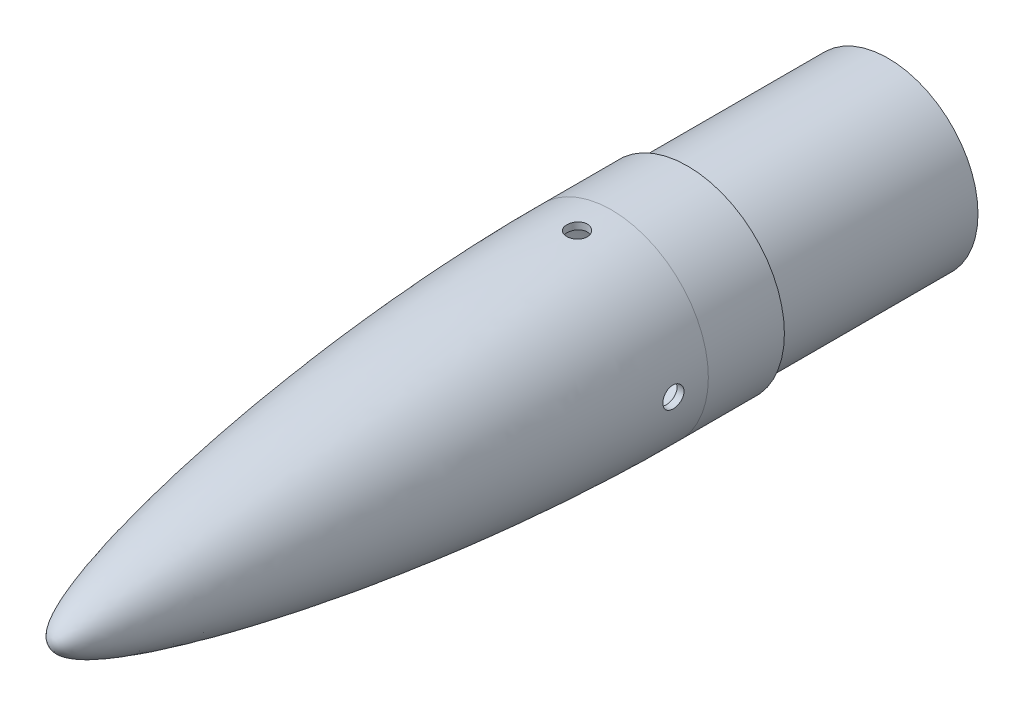
SolidWorks part; units mm, degrees
ref_plane "Alzado" through (0, 0, 0) normal (0, 0, 1) x (1, 0, 0)
ref_plane "Planta" through (0, 0, 0) normal (0, 1, 0) x (1, 0, 0)
ref_plane "Vista lateral" through (0, 0, 0) normal (1, 0, 0) x (0, 0, -1)
sketch "Croquis1" plane through (0, 0, 0) normal (0, 1, 0) x (1, 0, 0)
  line L0 (-12, 0) -> (12, 0) construction
  line L1 (-12, 0) -> (-12, -30)
  line L2 (-12, -30) -> (-13, -30)
  line L3 (-13, -30) -> (-13, -40)
  line L4 (0, 0) -> (0, -120) construction
  line L5 (-13, -92.4743) -> (-13, -27.4316) construction
  line L6 (22.3653, -120) -> (-22.3653, -120) construction
  line L7 (-13, 0) -> (-13, -29)
  line L8 (-13, -29) -> (-14, -29)
  line L9 (-14, -29) -> (-14, -40)
  line L10 (-13, 0) -> (-12, 0)
  line L11 (0, -121) -> (0, -120)
  spline S0 degree 3 poles (-13, -40) (-13, -79.4009) (-4.2587, -120) (0, -120) knots 0 0 0 0 1 1 1 1
  spline S1 degree 1 poles (-14, -40) (0, -121) knots 0 0 1 1 construction
  spline S2 degree 3 poles (-14, -40) (-14, -44.9352) (-13.7258, -54.8684) (-12.6483, -69.3606) (-11.0598, -82.9888) (-9.1149, -95.2593) (-7.3252, -103.9519) (-5.8667, -109.7487) (-4.777, -113.4608) (-3.7057, -116.4852) (-2.8356, -118.3965) (-2.1332, -119.5598) (-1.581, -120.2571) (-1.0426, -120.7072) (-0.4921, -120.9494) (-0.161, -121) (0, -121) knots 0 0 0 0 0.125 0.25 0.375 0.5 0.625 0.6875 0.75 0.8125 0.875 0.90625 0.9375 0.96875 0.984375 1 1 1 1
  point P4 (0, 0)
  dimension "D1" = 24
  dimension "D2" = 30
  dimension "D3" = 1
  dimension "D4" = 10
  dimension "D5" = 120
  dimension "D6" = 1
revolve "Revolución2" add sketch "Croquis1" angle 360 about L11
sketch "Croquis3" plane through (0, 0, 0) normal (0, 0, -1) x (-1, 0, 0)
  circle A0 centre (0, 0) radius 13
  dimension "D1" = 26
extrude "Extruir-Lámina1" add sketch "Croquis3" against normal up to surface (30 mm away) thin up to face at (12, 0, 30) thin type one direction reverse wall 2
sketch "Croquis10" plane through (0, 0, 0) normal (0, 1, 0) x (1, 0, 0)
  line L0 (0, 0) -> (0, -45) construction
  circle A0 centre (0, -45) radius 1.5
  dimension "D2" = 3
  dimension "D1" = 45
extrude "Cortar-Extruir1" cut sketch "Croquis10" against normal through all and the other way through all
sketch "Croquis11" plane through (0, 0, 0) normal (1, 0, 0) x (0, 0, -1)
  line L0 (0, 0) -> (-45, 0) construction
  circle A0 centre (-45, 0) radius 1.5
  dimension "D2" = 3
  dimension "D1" = 45
extrude "Cortar-Extruir2" cut sketch "Croquis11" against normal through all and the other way through all
thread "Rosca1" pitch 3.175 method cut profile "Perfil de rosca1" start angle 0, offset 10, length 20, pitch 3.175, diameter 22
ref_plane "Plano1" through (-11, 0, 20) normal (0, -1, 0) x (-1, 0, 0)
sketch "Perfil de rosca1" plane through (-11, 0, 20) normal (0, -1, 0) x (-1, 0, 0)
  line L0 (0, 0) -> (0, 3.175) construction
  line L1 (0, 0) -> (0, 2.6624)
  line L2 (0.254, 2.6624) -> (1.0668, 2.6624) construction
  line L3 (1.0668, 2.048) -> (1.0668, 1.6981)
  line L4 (0.8569, 2.2981) -> (0.2099, 2.4122)
  line L5 (0.8436, 1.1592) -> (0.2232, 0.5388)
  line L6 (0.762, 0) -> (1.0668, 0) construction
  arc A0 (0.2099, 2.4122) -> (0, 2.6624) centre (0.254, 2.6624) cw
  arc A1 (0.2232, 0.5388) -> (0, 0) centre (0.762, 0) ccw
  arc A2 (1.0668, 1.6981) -> (0.8436, 1.1592) centre (0.3048, 1.6981) cw
  arc A3 (1.0668, 2.048) -> (0.8569, 2.2981) centre (0.8128, 2.048) ccw
  point P10 (1.0668, 2.2611)
  point P17 (1.0668, 1.3824)
  point P18 (0, 2.4492)
  point P19 (0, 0.3156)
  point P20 (0, 0)
  dimension "RootFillet1" = 0.254
  dimension "RootFillet2" = 0.762
  dimension "CrestFillet2" = 0.762
  dimension "CrestFillet1" = 0.254
  dimension "Pitch" = 3.175
  dimension "Angle1" = 10
  dimension "Angle2" = 45
  dimension "a" = 2.1336
  dimension "b" = 1.0668
  dimension "c" = 0.8787
fillet "Redondeo1" radius 10 1 edges at (13, 0, 30)
